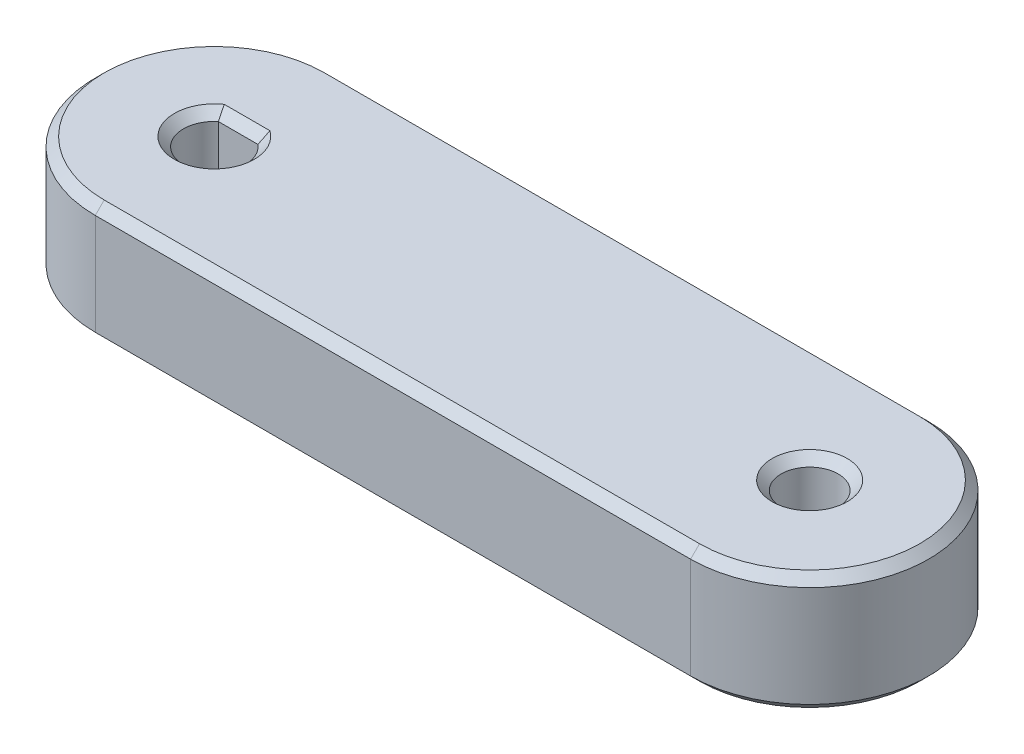
SolidWorks part; units mm, degrees
ref_plane "Front Plane" through (0, 0, 0) normal (0, 0, 1) x (1, 0, 0)
ref_plane "Top Plane" through (0, 0, 0) normal (0, 1, 0) x (1, 0, 0)
ref_plane "Right Plane" through (0, 0, 0) normal (1, 0, 0) x (0, 0, -1)
sketch "Sketch1" plane through (0, 0, 0) normal (0, 1, 0) x (1, 0, 0)
  line L0 (0, -10) -> (-50, -10)
  line L1 (0, 10) -> (-50, 10)
  line L2 (-51.6613, 2) -> (-48.3387, 2)
  circle A0 centre (0, 0) radius 2.4
  arc A1 (0, 10) -> (0, -10) centre (0, 0) cw
  circle A2 centre (-50, 0) radius 2.6
  arc A3 (-50, 10) -> (-50, -10) centre (-50, 0) ccw
  point P21 (0, 0)
  point P22 (-46.0108, 0)
  dimension "D1" = 4.8
  dimension "D4" = 2
  dimension "D5" = 5.2
  dimension "D2" = 50
  dimension "D3" = 20
extrude "Boss-Extrude1" add sketch "Sketch1" along normal blind 10 contours L1 A3 L0 A1 A0 A2 | L2 A2 region at (-24.9384, 0, 0) region at (-50, 0, -2.2425)
chamfer "Chamfer1" distance 0.75 angle 45 14 edges at (0, 0, 2.4) (0, 10, 2.4) (-25, 10, -10) (10, 10, 0) (-60, 10, 0) (-25, 10, 10) (-25, 0, -10) (10, 0, 0) (-60, 0, 0) (-25, 0, 10) (-50, 0, -2) (-50, 0, 2.6) (-50, 10, -2) (-50, 10, 2.6)
